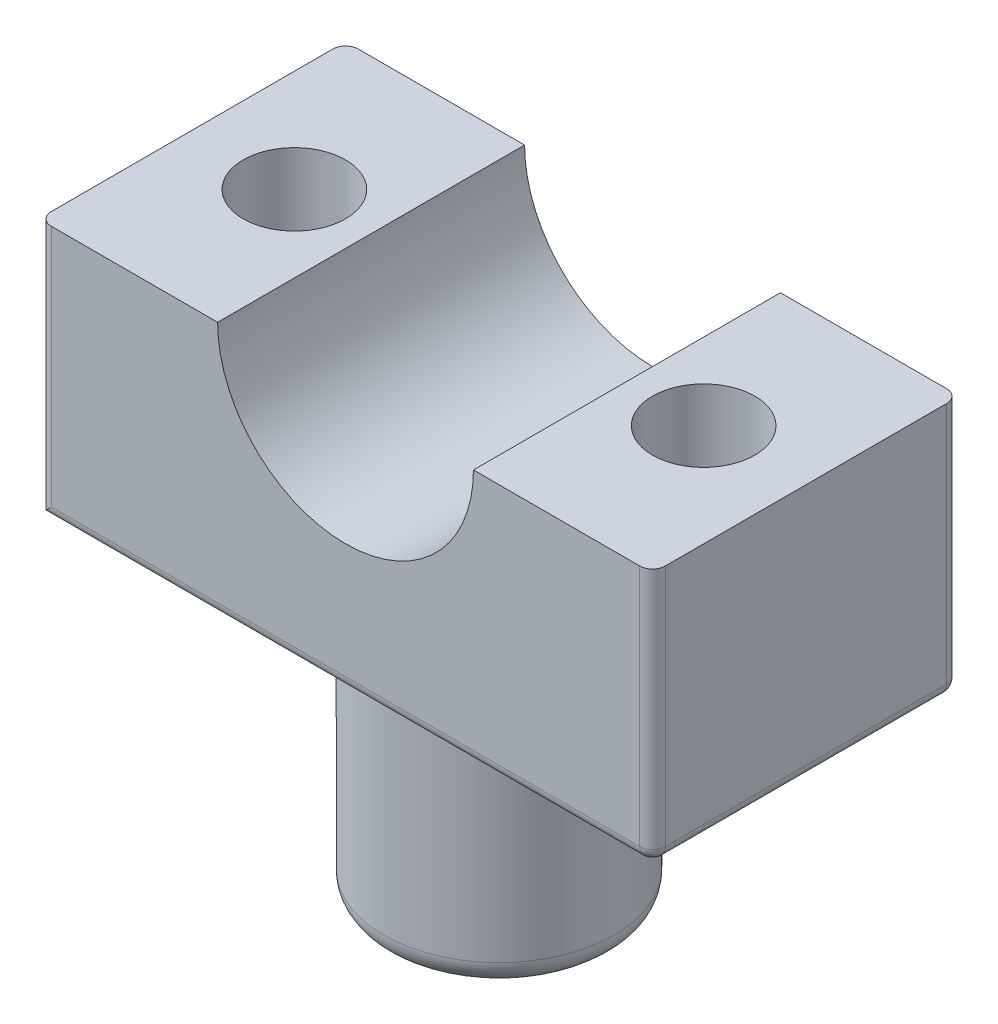
SolidWorks part; units mm, degrees
ref_plane "Front Plane" through (0, 0, 0) normal (0, 0, 1) x (1, 0, 0)
ref_plane "Top Plane" through (0, 0, 0) normal (0, 1, 0) x (1, 0, 0)
ref_plane "Right Plane" through (0, 0, 0) normal (1, 0, 0) x (0, 0, -1)
sketch "Sketch1" plane through (0, 0, 0) normal (0, 0, 1) x (1, 0, 0)
  line L0 (17, 10) -> (24, 10)
  line L1 (0, 0) -> (24, 0)
  line L2 (0, 0) -> (0, 10)
  line L3 (0, 10) -> (7, 10)
  line L4 (24, 0) -> (24, 10)
  arc A0 (7, 10) -> (17, 10) centre (12, 10) ccw
  dimension "D1" = 10
  dimension "D2" = 10
  dimension "D3" = 24
  dimension "D4" = 12
extrude "Boss-Extrude1" add sketch "Sketch1" along normal blind 12
sketch "Sketch2" plane through (0, 10, 0) normal (0, 1, 0) x (1, 0, 0)
  line L0 (12, 0) -> (12, -12) construction
  line L1 (17, 0) -> (7, 0) construction
  line L2 (7, -12) -> (17, -12) construction
  line L3 (7, 0) -> (0, 0) construction
  circle A0 centre (4, -6) radius 2
  circle A1 centre (20, -6) radius 2
  point P4 (0, 0)
  dimension "D3" = 4
  dimension "D1" = 6
  dimension "D2" = 8
extrude "Cut-Extrude1" cut sketch "Sketch2" against normal through all
sketch "Sketch3" plane through (0, 0, 0) normal (0, -1, 0) x (1, 0, 0)
  line L0 (0, 12) -> (24, 12) construction
  line L1 (0, 12) -> (0, 0) construction
  circle A0 centre (12, 6) radius 4.5
  circle A1 centre (12, 6) radius 2.5
  point P0 (4, 6)
  point P1 (20, 6)
  dimension "D3" = 9
  dimension "D4" = 5
  dimension "D1" = 6
  dimension "D2" = 12
extrude "Boss-Extrude2" add sketch "Sketch3" along normal blind 10
fillet "Fillet1" radius 1 2 edges at (12, -10, 1.5) (12, 0, 10.5)
fillet "Fillet2" radius 0.5 7 edges at (12, 0, 0) (0, 5, 0) (0, 5, 12) (24, 5, 0) (24, 5, 12) (24, 0, 6) (12, 0, 12)
